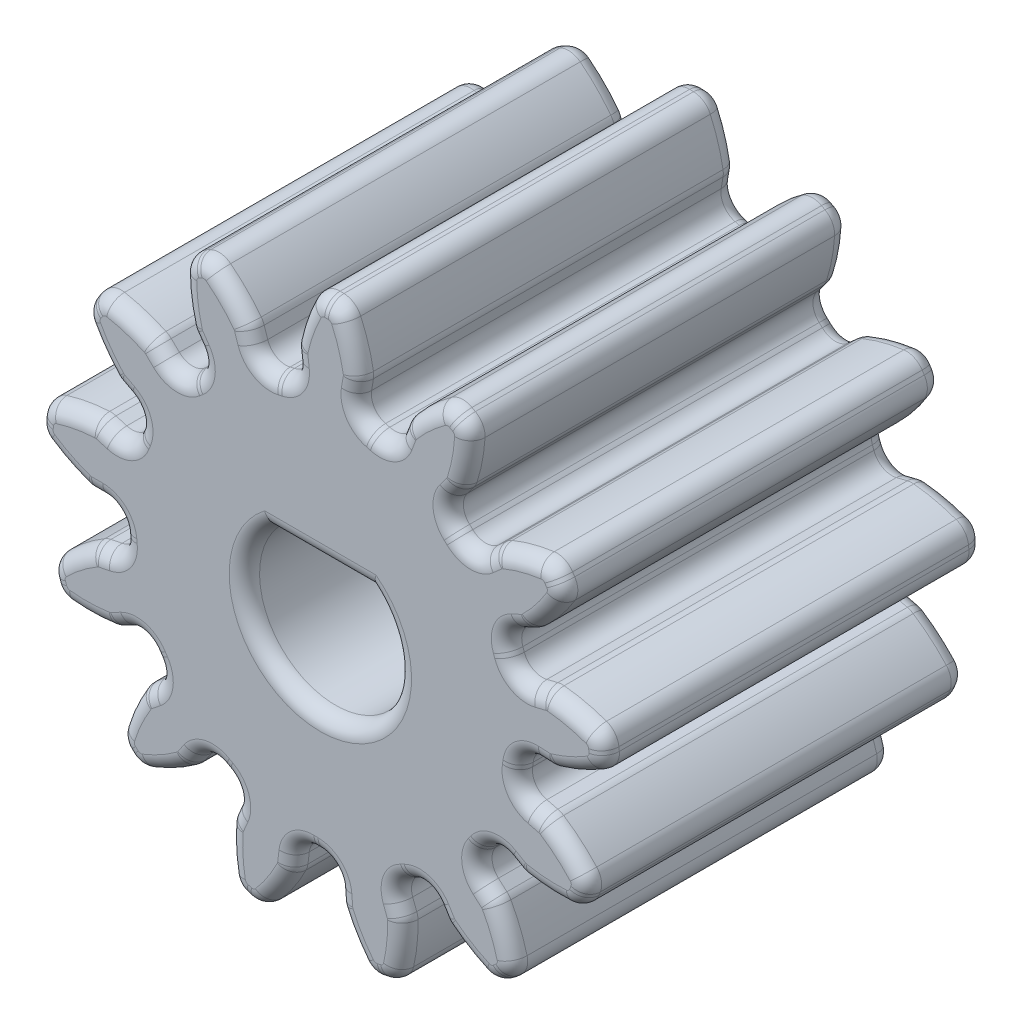
SolidWorks part; units mm, degrees
note: The reader was unsure of these and kept them because the rebuilt part matched: shared geometry of "Sketch1<14>".
ref_plane "Front Plane" through (0, 0, 0) normal (1, 0, 0) x (0, 1, 0)
ref_plane "Top Plane" through (0, 0, 0) normal (0, 0, 1) x (0, 1, 0)
ref_plane "Right Plane" through (0, 0, 0) normal (0, 1, 0) x (-1, 0, 0)
sketch "Sketch1" plane through (0, 0, 0) normal (0, 0, 1) x (0, 1, 0)
  line L1 (0, 0) -> (0, 6.108) construction
  line L2 (0, 0) -> (2.3374, 5.6431) construction
  line L3 (0, 0) -> (4.319, 4.319) construction
  line L4 (0, 0) -> (5.6431, 2.3374) construction
  line L5 (0, 0) -> (6.108, 0) construction
  line L6 (2.3374, 5.6431) -> (0.1214, 6.561) construction
  line L8 (4.319, 4.319) -> (0.9269, 7.7112) construction
  line L9 (5.6431, 2.3374) -> (2.8893, 8.9855) construction
  line L11 (6.108, 0) -> (6.108, 9.5944) construction
  line L12 (0, 0) -> (0.9306, 6.433) construction
  line L14 (1.7309, 5.8576) -> (0, 0) construction
  line L17 (0, 6.108) -> (0, 5.25)
  line L18 (1.7309, 5.8576) -> (1.4877, 5.0348)
  line L19 (0.1484, 6.4983) -> (0, 0) construction
  circle A16 centre (0, 0) radius 6.108 construction
  arc A17 (1.4236, 7.3636) -> (0.7214, 7.4652) centre (0, 0) ccw
  circle A18 centre (0, 0) radius 5.25
  arc A19 (0, 6.5) -> (1.8419, 6.2336) centre (0, 0) ccw construction
  arc A20 (0, 6.5) -> (1.8419, 6.2336) centre (0, 0) cw construction
  arc A21 (0, 6.108) -> (2.8893, 8.9855) centre (4.2724, 4.7074) cw construction
  arc A22 (1.7309, 5.8576) -> (-0.2246, 9.4359) centre (-2.7633, 5.7252) ccw construction
  arc A23 (0, 6.108) -> (0.7214, 7.4652) centre (4.2724, 4.7074) cw
  arc A24 (1.4236, 7.3636) -> (1.7309, 5.8576) centre (-2.7633, 5.7252) cw
  circle A25 centre (0, 0) radius 1.5
  point P12 (0, 0)
  dimension "BaseCircle" = 12.216
  dimension "AddendumCircle" = 15
  dimension "RootCircle" = 10.5
  dimension "PitchCircle" = 13
  dimension "D6" = 3
  dimension "D2" = 9.5944
  dimension "D3" = 7.1958
  dimension "D4" = 4.7972
  dimension "D5" = 2.3986
  dimension "D7" = 6.923
  dimension "D1" = 5
extrude "Boss-Extrude5" add sketch "Sketch1" along normal blind 10 contours A18 A19 A20
extrude "Boss-Extrude8" add sketch "Sketch1<14>" along normal blind 10 contours A24 A17 A23 A16
sketch "Sketch1<14>" plane through (0, 0, 0) normal (0, 0, 1) x (0, 1, 0) same geometry as "Sketch1"
sketch "Sketch4" plane through (0, 0, 10) normal (0, 0, 1) x (1, 0, 0)
  line L0 (0, -2) -> (0, 2) construction
  line L1 (-1.3229, 1.5) -> (1.3229, 1.5)
  circle A1 centre (0, 0) radius 1.5 construction
  circle A2 centre (0, 0) radius 1.5 construction
  arc A3 (-1.3229, 1.5) -> (1.3229, 1.5) centre (0, 0) ccw
  point P8 (0, 0)
  dimension "D1" = 4
  dimension "D2" = 3.5
extrude "Cut-Extrude1" cut sketch "Sketch4" against normal blind 10
sketch "Sketch5" plane through (0, 0, 0) normal (0, 0, -1) x (1, 0, 0)
  line L0 (1.3229, -1.5) -> (-1.3229, -1.5) construction
  line L1 (1.3229, -1.5) -> (-1.3229, -1.5)
  circle A0 centre (0, 0) radius 3.6
  arc A1 (1.3229, -1.5) -> (-1.3229, -1.5) centre (0, 0) ccw construction
  arc A2 (1.3229, -1.5) -> (-1.3229, -1.5) centre (0, 0) ccw
  dimension "D1" = 1.6
extrude "Boss-Extrude7" add sketch "Sketch5" along normal blind 1
fillet "Fillet6" radius 0.5 6 edges at (-7.3636, 1.4236, 5) (-7.4652, 0.7214, 5) (-6.108, 0, 5) (-5.25, 0, 5) (-5.8576, 1.7309, 5) (-5.0348, 1.4877, 5)
pattern_circular "CirPattern1" count 13 over 360 about axis through (0, 0, 0) along (0, 0, 1) of "Boss-Extrude8", "Fillet6"
fillet "Fillet7" radius 0.4 318 edges at (-0.5193, -5.3669, 0) (-0.5193, -5.3669, 10) (-2.2601, -4.8955, 0) (-2.2601, -4.8955, 10) (-5.1003, -5.4989, 0) (-5.1003, -5.4989, 10) (-2.5453, -4.5917, 0) (-3.3385, -4.8367, 0) (-4.023, -5.3864, 0) (-5.0691, -4.4162, 0) (-4.5722, -3.6923, 0) (-4.7486, -3.8438, 0) (-3.4763, -5.0239, 0) (-4.8157, -5.6565, 0) (-5.2789, -5.227, 0) (-5.0691, -4.4162, 10) (-4.5722, -3.6923, 10) (-4.023, -5.3864, 10) (-3.3385, -4.8367, 10) (-2.5453, -4.5917, 10) (-4.7486, -3.8438, 10) (-3.4763, -5.0239, 10) (-4.8157, -5.6565, 10) (-5.2789, -5.227, 10) (-2.954, -4.5108, 0) (-2.954, -4.5108, 10) (-4.2762, -3.2844, 0) (-4.2762, -3.2844, 10) (-7.0715, -2.4988, 0) (-7.0715, -2.4988, 10) (-4.3876, -2.8829, 0) (-5.2038, -2.7312, 0) (-6.0654, -2.8999, 0) (-6.5408, -1.5547, 0) (-5.7644, -1.1446, 0) (-5.991, -1.1968, 0) (-5.4129, -2.8329, 0) (-6.8928, -2.7706, 0) (-7.1033, -2.175, 0) (-6.5408, -1.5547, 10) (-5.7644, -1.1446, 10) (-6.0654, -2.8999, 10) (-5.2038, -2.7312, 10) (-4.3876, -2.8829, 10) (-5.991, -1.1968, 10) (-5.4129, -2.8329, 10) (-6.8928, -2.7706, 10) (-7.1033, -2.175, 10) (-4.7119, -2.6214, 0) (-4.7119, -2.6214, 10) (-5.3128, -0.9209, 0) (-5.3128, -0.9209, 10) (-6.0735, 4.4003, 0) (-6.0735, 4.4003, 10) (-4.8651, 1.9732, 0) (-5.2038, 2.7312, 0) (-5.8321, 3.3444, 0) (-4.995, 4.4998, 0) (-4.2165, 4.0938, 0) (-4.3882, 4.2507, 0) (-5.4063, 2.8454, 0) (-6.1958, 4.0988, 0) (-5.8251, 4.6103, 0) (-4.995, 4.4998, 10) (-4.2165, 4.0938, 10) (-5.8321, 3.3444, 10) (-5.2038, 2.7312, 10) (-4.8651, 1.9732, 10) (-4.3882, 4.2507, 10) (-5.4063, 2.8454, 10) (-6.1958, 4.0988, 10) (-5.8251, 4.6103, 10) (0, 1.5, 10) (-4.834, 2.3887, 0) (-4.834, 2.3887, 10) (0, -2, 10) (-3.7759, 3.8492, 0) (-3.7759, 3.8492, 10) (-3.3329, 6.7187, 0) (-3.3329, 6.7187, 10) (-3.3908, 4.0081, 0) (-3.3385, 4.8367, 0) (-3.6098, 5.6717, 0) (-2.3317, 6.3057, 0) (-1.8311, 5.5844, 0) (-1.9102, 5.8031, 0) (-3.4647, 5.0319, 0) (-3.5813, 6.5086, 0) (-3.0154, 6.7893, 0) (-2.3317, 6.3057, 10) (-1.8311, 5.5844, 10) (-3.6098, 5.6717, 10) (-3.3385, 4.8367, 10) (-3.3908, 4.0081, 10) (-1.9102, 5.8031, 10) (-3.4647, 5.0319, 10) (-3.5813, 6.5086, 10) (-3.0154, 6.7893, 10) (-3.1702, 4.3616, 0) (-3.1702, 4.3616, 10) (-1.5546, 5.163, 0) (-1.5546, 5.163, 10) (3.6, 0, 0) (-3.6, 0, -1) (0, -2, -1) (0, 1.5, -1) (0.1712, 7.498, 0) (0.1712, 7.498, 10) (-1.1397, 5.1248, 0) (-0.7084, 5.8341, 0) (-0.5606, 6.6996, 0) (0.8658, 6.667, 0) (0.9739, 5.7957, 0) (1.0055, 6.0261, 0) (-0.7294, 6.0657, 0) (-0.1464, 7.4274, 0) (0.4852, 7.413, 0) (0.8658, 6.667, 10) (0.9739, 5.7957, 10) (-0.5606, 6.6996, 10) (-0.7084, 5.8341, 10) (-1.1397, 5.1248, 10) (1.0055, 6.0261, 10) (-0.7294, 6.0657, 10) (-0.1464, 7.4274, 10) (0.4852, 7.413, 10) (-0.7802, 5.3352, 0) (-0.7802, 5.3352, 10) (1.0228, 5.2941, 0) (1.0228, 5.2941, 10) (3.6361, 6.5596, 0) (3.6361, 6.5596, 10) (-7.4227, 1.0737, 0) (1.3724, 5.0674, 0) (2.084, 5.4951, 0) (2.6171, 6.1927, 0) (3.8649, 5.501, 0) (3.5557, 4.6793, 0) (3.6907, 4.8686, 0) (-7.4227, 1.0737, 10) (2.173, 5.7099, 0) (3.3221, 6.6446, 0) (3.8746, 6.3384, 0) (3.8649, 5.501, 10) (3.5557, 4.6793, 10) (2.6171, 6.1927, 10) (2.084, 5.4951, 10) (1.3724, 5.0674, 10) (3.6907, 4.8686, 10) (2.173, 5.7099, 10) (3.3221, 6.6446, 10) (3.8746, 6.3384, 10) (-5.2248, -0.5137, 0) (-5.877, 0, 0) (1.7886, 5.0867, 0) (1.7886, 5.0867, 10) (3.366, 4.2123, 0) (-6.7183, 0.251, 0) (3.366, 4.2123, 10) (-6.514, 1.6631, 0) (-5.6361, 1.6654, 0) (-5.8609, 1.7245, 0) (-6.1094, 0.007, 0) (-7.3909, 0.75, 0) (6.268, 4.1185, 0) (6.268, 4.1185, 10) (-7.3004, 1.3752, 0) (3.5702, 3.8492, 0) (4.399, 3.8972, 0) (5.1952, 4.2672, 0) (5.9786, 3.0748, 0) (5.323, 2.4908, 0) (5.5305, 2.5957, 0) (4.5776, 4.046, 0) (-6.514, 1.6631, 10) (6.0295, 4.3397, 0) (6.3764, 3.8118, 0) (5.9786, 3.0748, 10) (5.323, 2.4908, 10) (5.1952, 4.2672, 10) (4.399, 3.8972, 10) (3.5702, 3.8492, 10) (5.5305, 2.5957, 10) (4.5776, 4.046, 10) (6.0295, 4.3397, 10) (6.3764, 3.8118, 10) (-5.2248, -0.5137, 10) (-5.6361, 1.6654, 10) (3.9476, 3.6728, 0) (3.9476, 3.6728, 10) (4.938, 2.1656, 0) (-6.7183, 0.251, 10) (4.938, 2.1656, 10) (-5.877, 0, 10) (-5.8609, 1.7245, 10) (-6.1094, 0.007, 10) (-7.3909, 0.75, 10) (-7.3004, 1.3752, 10) (7.464, 0.7339, 0) (7.464, 0.7339, 10) (4.95, 1.7492, 0) (5.7062, 1.4065, 0) (6.5832, 1.3641, 0) (6.7228, -0.0558, 0) (5.8708, -0.2682, 0) (6.1033, -0.2718, 0) (5.9335, 1.4552, 0) (7.3556, 1.0406, 0) (7.4174, 0.4119, 0) (6.7228, -0.0558, 10) (5.8708, -0.2682, 10) (6.5832, 1.3641, 10) (5.7062, 1.4065, 10) (4.95, 1.7492, 10) (6.1033, -0.2718, 10) (5.9335, 1.4552, 10) (7.3556, 1.0406, 10) (7.4174, 0.4119, 10) (5.2023, 1.4176, 0) (5.2023, 1.4176, 10) (5.3788, -0.3773, 0) (5.3788, -0.3773, 10) (-5.3904, -0.1314, 0) (-5.3904, -0.1314, 10) (-5.1322, 1.6535, 0) (-5.1322, 1.6535, 10) (6.9501, -2.8189, 0) (6.9501, -2.8189, 10) (5.1959, -0.7516, 0) (5.7062, -1.4065, 0) (6.463, -1.8515, 0) (5.9268, -3.1736, 0) (5.0737, -2.9658, 0) (5.2779, -3.077, 0) (5.9302, -1.4689, 0) (6.9966, -2.4969, 0) (6.7592, -3.0823, 0) (5.9268, -3.1736, 10) (5.0737, -2.9658, 10) (6.463, -1.8515, 10) (5.7062, -1.4065, 10) (5.1959, -0.7516, 10) (5.2779, -3.077, 10) (5.9302, -1.4689, 10) (6.9966, -2.4969, 10) (6.7592, -3.0823, 10) (5.2652, -1.1624, 0) (5.2652, -1.1624, 10) (4.5874, -2.8337, 0) (4.5874, -2.8337, 10) (4.844, -5.7259, 0) (4.844, -5.7259, 10) (4.2515, -3.0802, 0) (4.399, -3.8972, 0) (4.8623, -4.643, 0) (3.773, -5.5644, 0) (3.1143, -4.984, 0) (3.2434, -5.1773, 0) (4.5683, -4.0565, 0) (5.0348, -5.4624, 0) (4.5526, -5.8704, 0) (3.773, -5.5644, 10) (3.1143, -4.984, 10) (4.8623, -4.643, 10) (4.399, -3.8972, 10) (4.2515, -3.0802, 10) (3.2434, -5.1773, 10) (4.5683, -4.0565, 10) (5.0348, -5.4624, 10) (4.5526, -5.8704, 10) (4.1219, -3.4761, 0) (4.1219, -3.4761, 10) (2.745, -4.6409, 0) (2.745, -4.6409, 10) (1.6282, -7.3211, 0) (1.6282, -7.3211, 10) (2.3331, -4.7031, 0) (2.084, -5.4951, 0) (2.1476, -6.3707, 0) (0.7549, -6.6805, 0) (0.4414, -5.8604, 0) (0.4659, -6.0916, 0) (2.1598, -5.7149, 0) (1.9196, -7.1765, 0) (1.303, -7.3137, 0) (0.7549, -6.6805, 10) (0.4414, -5.8604, 10) (2.1476, -6.3707, 10) (2.084, -5.4951, 10) (2.3331, -4.7031, 10) (0.4659, -6.0916, 10) (2.1598, -5.7149, 10) (1.9196, -7.1765, 10) (1.303, -7.3137, 10) (2.0343, -4.9935, 0) (2.0343, -4.9935, 10) (0.2738, -5.385, 0) (0.2738, -5.385, 10) (-1.9606, -7.2392, 0) (-1.9606, -7.2392, 10) (-0.1198, -5.2486, 0) (-0.7084, -5.8341, 0) (-1.059, -6.6391, 0) (-2.4361, -6.2661, 0) (-2.3326, -5.3942, 0) (-2.4184, -5.6103, 0) (-0.7434, -6.064, 0) (-1.6354, -7.2466, 0) (-2.2451, -7.0815, 0) (-2.4361, -6.2661, 10) (-2.3326, -5.3942, 10) (-1.059, -6.6391, 10) (-0.7084, -5.8341, 10) (-0.1198, -5.2486, 10) (-2.4184, -5.6103, 10) (-0.7434, -6.064, 10) (-1.6354, -7.2466, 10) (-2.2451, -7.0815, 10)
equation "\"NumberOfTeeth\"= 13"
equation "\"Module\"= 1"
equation "\"PressureAngle\"= 20deg"
equation "\"PitchDiameter\"= \"NumberOfTeeth\" * \"Module\""
equation "\"OutsideDiameter\"= (\"NumberOfTeeth\" + 2) * \"Module\""
equation "\"WholeDepthDia\"= (\"NumberOfTeeth\" - 2.5) * \"Module\""
equation "\"BaseCircleDia\"= \"PitchDiameter\" * cos(\"PressureAngle\")"
equation "\"Addendum\"= 1 * \"Module\""
equation "\"Dedendum\"= 1.25 * \"Module\""
equation "\"WholeDepth\"= 2.25 * \"Module\""
equation "\"CircularPitch\"= 360 / \"NumberOfTeeth\""
equation "\"FilletRadius\"= \"Module\" / 2"
equation "\"PitchArcLength\"= ( \"CircularPitch\" / 180 * 3.14 * \"BaseCircleDia\" / 2 )"
equation "\"BaseCircle@Sketch1\" = \"BaseCircleDia\""
equation "\"AddendumCircle@Sketch1\"= \"PitchCircle@Sketch1\" + \"Addendum\" * 2"
equation "\"RootCircle@Sketch1\"=\"PitchCircle@Sketch1\" - \"Dedendum\" * 2"
equation "\"PitchCircle@Sketch1\" = \"Module\" * \"NumberOfTeeth\""
equation "\"InvoluteArrayMaxLength\"= \"BaseCircleDia\" * pi / 4"
equation "\"D2@Sketch1\"=\"InvoluteArrayMaxLength\""
equation "\"D3@Sketch1\"=\"InvoluteArrayMaxLength\"*3/4"
equation "\"D4@Sketch1\"=\"InvoluteArrayMaxLength\"*2/4"
equation "\"D5@Sketch1\"=\"InvoluteArrayMaxLength\"*1/4"
equation "\"GearWidth\"=10"
equation "\"ShaftDiameter\"= 3"
equation "\"D6@Sketch1\" = IIF ( \"PitchCircle@Sketch1\" > \"ShaftDiameter\" , \"ShaftDiameter\" , \"PitchCircle@Sketch1\" - 3 )"
equation "\"D1\"= \"NumberOfTeeth\""
equation "\"D1\"= \"GearWidth\""
equation "\"D7@Sketch1\"=\"CircularPitch\"/4"
equation "\"D1\"= \"FilletRadius\""
equation "\"D1@CirPattern1\"=\"NumberOfTeeth\""
